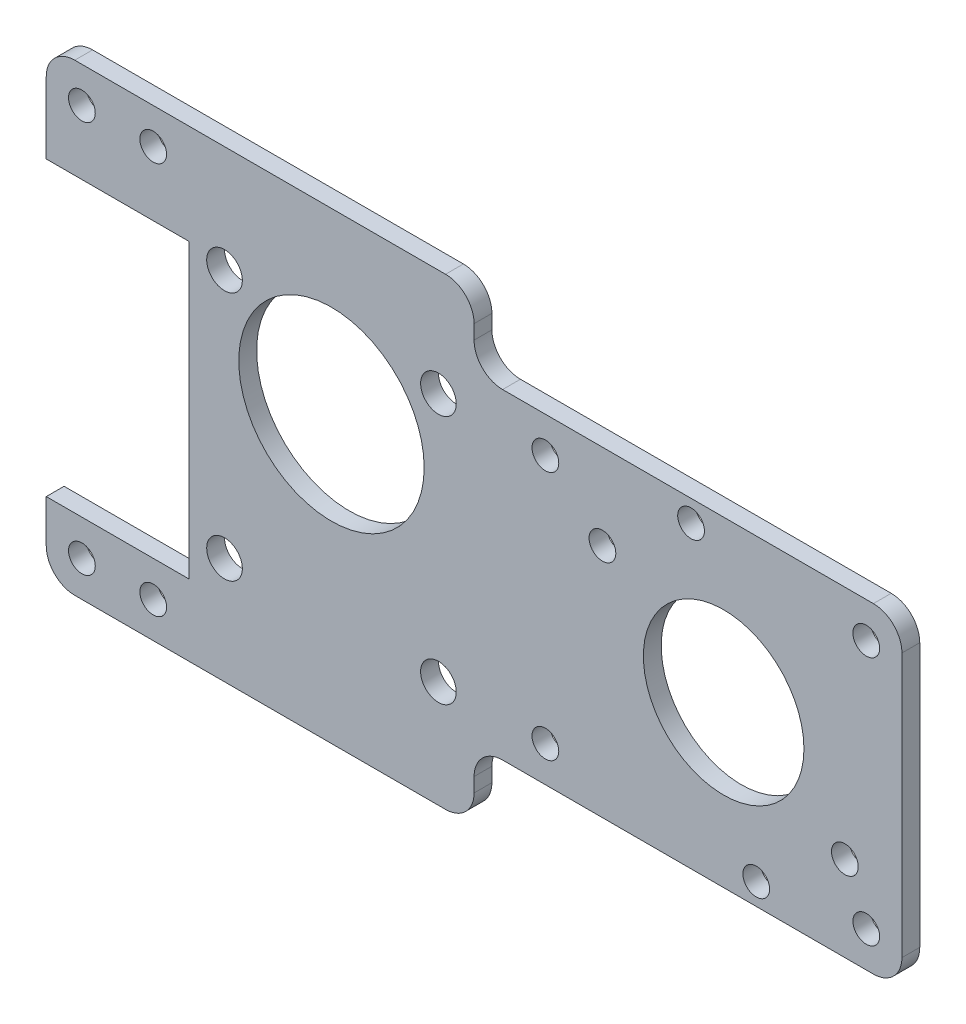
SolidWorks part; units mm, degrees
ref_plane "Front Plane" through (0, 0, 0) normal (0, 0, 1) x (1, 0, 0)
ref_plane "Top Plane" through (0, 0, 0) normal (0, 1, 0) x (1, 0, 0)
ref_plane "Right Plane" through (0, 0, 0) normal (1, 0, 0) x (0, 0, -1)
sketch "Sketch1" plane through (0, 0, 0) normal (0, 0, 1) x (1, 0, 0)
  line L1 (-63.5, 28.575) -> (63.5, 28.575)
  line L2 (-63.5, 28.575) -> (-63.5, -28.575)
  line L3 (-63.5, -28.575) -> (63.5, -28.575)
  line L4 (63.5, 28.575) -> (63.5, -28.575)
  line L5 (-63.5, 28.575) -> (63.5, -28.575) construction
  line L6 (-63.5, -28.575) -> (63.5, 28.575) construction
  circle A0 centre (31.75, 0) radius 14.3002
  circle A1 centre (31.75, 0) radius 25.4 construction
  circle A2 centre (37.5551, -24.7277) radius 2.3812
  circle A3 centre (18.3697, -21.59) radius 2.3813
  circle A4 centre (7.0223, -5.8051) radius 2.3813
  circle A5 centre (10.16, 13.3803) radius 2.3813
  circle A6 centre (25.9449, 24.7277) radius 2.3813
  circle A7 centre (45.1303, 21.59) radius 2.3812
  circle A8 centre (56.4777, 5.8051) radius 2.3812
  circle A9 centre (53.34, -13.3803) radius 2.3812
  point P0 (0, 0)
  point P12 (0, 0)
  point P13 (34.382, -23.64)
  point P27 (31.75, 0)
  point P28 (0, 0)
  point P29 (30.9419, -24.7881)
  dimension "D3" = 28.6004
  dimension "D5" = 50.8
  dimension "D8" = 4.7625
  dimension "D1" = 127
  dimension "D2" = 57.15
  dimension "D4" = 31.75
  dimension "D7" = 21.59
  dimension "D6" = 8
extrude "Boss-Extrude1" add sketch "Sketch1" along normal blind 3.175 contours A8 L4 L1 L2 L3 A9 A7 A6 A5 A4 A3 A2 A0 | L4 A8 | A3 | A4 | A7 region at (-3.8501, 0, 0) region at (18.3697, -21.59, 0) region at (7.0223, -5.8051, 0) region at (45.1303, 21.59, 0) region at (56.4777, 5.8051, 0)
sketch "Sketch2" plane through (0, 0, 3.175) normal (0, 0, 1) x (1, 0, 0)
  line L0 (-63.5, 28.575) -> (63.5, 28.575) construction
  line L1 (63.5, 28.575) -> (63.5, -28.575) construction
  line L2 (-63.5, -28.575) -> (63.5, -28.575) construction
  circle A0 centre (57.15, 22.225) radius 2.3812
  circle A1 centre (57.15, -22.225) radius 2.3812
  circle A2 centre (0, 22.225) radius 2.3813
  circle A3 centre (0, -22.225) radius 2.3813
  dimension "D1" = 4.7625
  dimension "D4" = 4.7625
  dimension "D7" = 4.7625
  dimension "D8" = 4.7625
  dimension "D2" = 6.35
  dimension "D3" = 6.35
  dimension "D5" = 6.35
  dimension "D6" = 6.35
  dimension "D9" = 57.15
  dimension "D10" = 57.15
  dimension "D11" = 6.35
  dimension "D12" = 6.35
extrude "Cut-Extrude1" cut sketch "Sketch2" against normal blind 3.175
fillet "Fillet1" radius 5.08 2 edges at (63.5, -28.575, 1.5875) (63.5, 28.575, 1.5875)
sketch "Sketch3" plane through (0, 0, 3.175) normal (0, 0, 1) x (1, 0, 0)
  line L0 (-63.5, 28.575) -> (-63.5, -28.575) construction
  line L1 (-63.5, 28.575) -> (58.42, 28.575) construction
  line L2 (-63.5, 0) -> (63.5, 0) construction
  line L3 (63.5, 23.495) -> (63.5, -23.495) construction
  circle A0 centre (-57.15, 22.225) radius 3.175
  circle A1 centre (-19.05, 22.225) radius 3.175
  circle A2 centre (-19.05, -22.225) radius 3.175
  circle A3 centre (-57.15, -22.225) radius 3.175
  dimension "D3" = 6.35
  dimension "D4" = 6.35
  dimension "D1" = 6.35
  dimension "D2" = 6.35
  dimension "D5" = 38.1
extrude "Cut-Extrude2" cut sketch "Sketch3" against normal blind 3.175
sketch "Sketch4" plane through (0, 0, 3.175) normal (0, 0, 1) x (1, 0, 0)
  line L0 (-63.5, 28.575) -> (58.42, 28.575) construction
  line L1 (-63.5, 28.575) -> (-63.5, -28.575) construction
  circle A0 centre (-38.1, 9.525) radius 16.51
  dimension "D1" = 33.02
  dimension "D2" = 19.05
  dimension "D3" = 25.4
extrude "Cut-Extrude3" cut sketch "Sketch4" against normal blind 7.62
sketch "Sketch5" plane through (0, 0, 3.175) normal (0, 0, 1) x (1, 0, 0)
  line L0 (-63.5, -28.575) -> (58.42, -28.575) construction
  line L1 (-12.7, -28.575) -> (-88.9, -28.575)
  line L2 (-12.7, -28.575) -> (-12.7, -41.275)
  line L3 (-12.7, -41.275) -> (-88.9, -41.275)
  line L4 (-88.9, -28.575) -> (-88.9, -41.275)
  line L5 (-63.5, 28.575) -> (-63.5, -28.575) construction
  line L6 (-63.5, 28.575) -> (58.42, 28.575) construction
  line L7 (-12.7, 28.575) -> (-88.9, 28.575)
  line L8 (-12.7, 28.575) -> (-12.7, 41.275)
  line L9 (-12.7, 41.275) -> (-88.9, 41.275)
  line L10 (-88.9, 28.575) -> (-88.9, 41.275)
  dimension "D1" = 50.8
  dimension "D2" = 12.7
  dimension "D3" = 25.4
  dimension "D4" = 12.7
  dimension "D5" = 25.4
  dimension "D6" = 50.8
extrude "Boss-Extrude2" add sketch "Sketch5" against normal blind 3.175
fillet "Fillet2" radius 5.08 4 edges at (-12.7, -41.275, 1.5875) (-12.7, -28.575, 1.5875) (-12.7, 41.275, 1.5875) (-12.7, 28.575, 1.5875)
sketch "Sketch6" plane through (0, 0, 3.175) normal (0, 0, 1) x (1, 0, 0)
  line L0 (-88.9, 41.275) -> (-88.9, 28.575) construction
  line L1 (-63.5, 28.575) -> (-88.9, 28.575)
  line L2 (-63.5, 28.575) -> (-63.5, 23.495)
  line L3 (-63.5, 23.495) -> (-88.9, 23.495)
  line L4 (-88.9, 28.575) -> (-88.9, 23.495)
  line L5 (-63.5, -28.575) -> (-88.9, -28.575) construction
  dimension "D1" = 52.07
extrude "Boss-Extrude3" add sketch "Sketch6" against normal blind 3.175
fillet "Fillet3" radius 5.08 2 edges at (-88.9, 41.275, 1.5875) (-88.9, -41.275, 1.5875)
sketch "Sketch7" plane through (0, 0, 3.175) normal (0, 0, 1) x (1, 0, 0)
  line L0 (-88.9, -28.575) -> (-88.9, -36.195) construction
  line L1 (-88.9, 36.195) -> (-88.9, 23.495) construction
  line L2 (-83.82, -41.275) -> (-17.78, -41.275) construction
  line L3 (-17.78, 41.275) -> (-83.82, 41.275) construction
  line L4 (-17.78, 41.275) -> (-83.82, 41.275) construction
  circle A0 centre (-82.55, 34.925) radius 2.3813
  circle A1 centre (-82.55, -34.925) radius 2.3813
  circle A2 centre (-69.85, 34.925) radius 2.3813
  circle A3 centre (-69.85, -34.925) radius 2.3813
  dimension "D1" = 4.7625
  dimension "D2" = 4.7625
  dimension "D7" = 4.7625
  dimension "D8" = 4.7625
  dimension "D3" = 6.35
  dimension "D4" = 6.35
  dimension "D5" = 6.35
  dimension "D6" = 6.35
  dimension "D9" = 6.35
  dimension "D10" = 6.35
  dimension "D11" = 12.7
  dimension "D12" = 12.7
extrude "Cut-Extrude4" cut sketch "Sketch7" against normal blind 3.175
